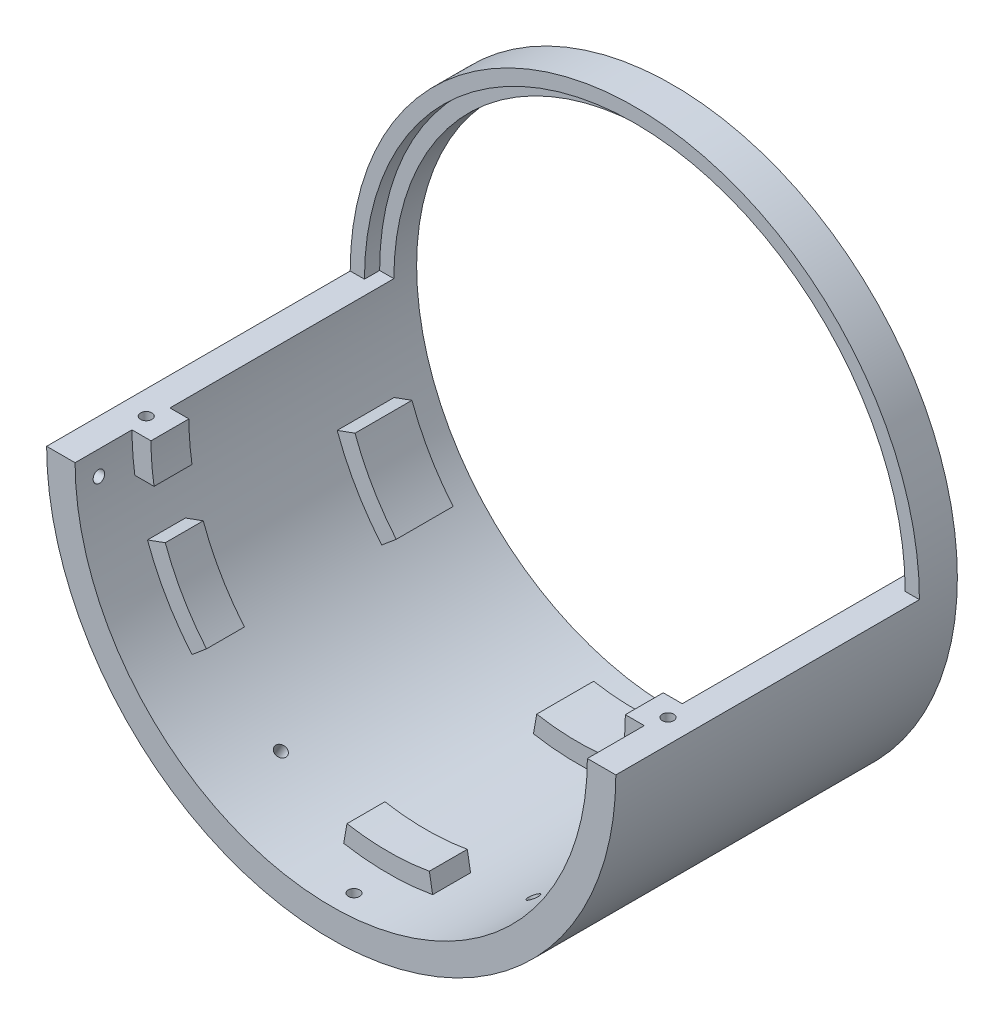
SolidWorks part; units mm, degrees
ref_plane "Front Plane" through (0, 0, 0) normal (0, 0, 1) x (1, 0, 0)
ref_plane "Top Plane" through (0, 0, 0) normal (0, 1, 0) x (1, 0, 0)
ref_plane "Right Plane" through (0, 0, 0) normal (1, 0, 0) x (0, 0, -1)
sketch "Sketch2" plane through (0, 0, 0) normal (0, 0, 1) x (1, 0, 0)
  circle A0 centre (0, 0) radius 67.5
  circle A1 centre (0, 0) radius 75
  dimension "D1" = 135
  dimension "D2" = 7.5
extrude "Boss-Extrude2" add sketch "Sketch2" along normal blind 10
sketch "Sketch3" plane through (0, 0, 10) normal (0, 0, 1) x (1, 0, 0)
  line L0 (67.5, 0) -> (75, 0)
  line L1 (-67.5, 0) -> (-75, 0)
  circle A0 centre (0, 0) radius 67.5
  circle A1 centre (0, 0) radius 75
  circle M1 centre (0, 0) radius 75
  circle M2 centre (0, 0) radius 67.5
  dimension "D1" = 135
  dimension "D2" = 7.5
extrude "Boss-Extrude3" add sketch "Sketch3" along normal blind 80 contours L1 L0 M2 M1 region at (71.25, -1.6771, 10)
sketch "Sketch5" plane through (0, 0, 10) normal (0, 0, 1) x (1, 0, 0)
  line L0 (-58.7308, -21.3763) -> (-63.4293, -23.0864)
  line L1 (-10.853, -61.5505) -> (-11.7213, -66.4745)
  line L2 (10.853, -61.5505) -> (11.7213, -66.4745)
  line L3 (-47.8778, -40.1742) -> (-51.708, -43.3882)
  line L4 (-67.5, 0) -> (-75, 0) construction
  line L5 (63.4293, -23.0864) -> (58.7308, -21.3763)
  line L6 (51.708, -43.3882) -> (47.8778, -40.1742)
  line L7 (67.5, 0) -> (75, 0) construction
  circle A0 centre (0, 0) radius 62.5
  circle A1 centre (0, 0) radius 67.5
  dimension "D1" = 125
  dimension "D2" = 5
  dimension "D3" = 20
  dimension "D4" = 4.924
  dimension "D5" = 20
  dimension "D6" = 20
  dimension "D7" = 20
  dimension "D8" = 20
extrude "Boss-Extrude4" add sketch "Sketch5" along normal blind 15 contours L0 A1 L3 A0 | L1 A1 L2 A0 | L6 A1 L5 A0 region at (-56.0339, -32.3512, 10) region at (56.0339, -32.3512, 10) region at (0, -64.7024, 10)
ref_plane "Plane1" through (0, 0, 65) normal (0, 0, 1) x (1, 0, 0)
sketch "Sketch6" plane through (0, 0, 65) normal (0, 0, 1) x (1, 0, 0)
  line L0 (-58.7308, -21.3763) -> (-63.4293, -23.0864)
  line L1 (-10.853, -61.5505) -> (-11.7213, -66.4745)
  line L2 (10.853, -61.5505) -> (11.7213, -66.4745)
  line L3 (-47.8778, -40.1742) -> (-51.708, -43.3882)
  line L5 (63.4293, -23.0864) -> (58.7308, -21.3763)
  line L6 (51.708, -43.3882) -> (47.8778, -40.1742)
  circle A0 centre (0, 0) radius 62.5
  circle A1 centre (0, 0) radius 67.5
  dimension "D1" = 125
  dimension "D2" = 5
  dimension "D3" = 20
  dimension "D4" = 4.924
  dimension "D6" = 20
  dimension "D8" = 20
extrude "Boss-Extrude5" add sketch "Sketch6" along normal blind 10 contours L0 A1 L3 A0 | L1 A1 L2 A0 | L6 A1 L5 A0 region at (-56.0339, -32.3512, 65) region at (56.0339, -32.3512, 65) region at (0, -64.7024, 65)
ref_plane "Plane2" through (67.5, 0, 0) normal (-1, 0, 0) x (0, 0, 1)
sketch "Sketch7" plane through (67.5, 0, 0) normal (-1, 0, 0) x (0, 0, 1)
  line L0 (65, 0) -> (75, 0)
  line L1 (90, 0) -> (10, 0) construction
  line L2 (65, -39.875) -> (65, 39.875) construction
  line L3 (75, 0) -> (75, -10)
  line L4 (75, -10) -> (65, -10)
  line L5 (65, -10) -> (65, 0)
  line L6 (65, -23.0864) -> (65, -43.3882) construction
  line L7 (75, -43.3882) -> (75, -23.0864) construction
  point P12 (33.0903, 2.3101)
  dimension "D2" = 10
extrude "Boss-Extrude6" add sketch "Sketch7" along normal blind 137
sketch "Sketch8" plane through (0, 0, 10) normal (0, 0, 1) x (1, 0, 0)
  line L0 (-67.5, 0) -> (67.5, 0) construction
  circle A0 centre (0, 0) radius 62.5
  dimension "D1" = 125
extrude "Cut-Extrude1" cut sketch "Sketch8" along normal blind 150
sketch "Sketch9" plane through (0, 0, 0) normal (0, 1, 0) x (1, 0, 0)
  line L0 (-75, -90) -> (-75, -10) construction
  line L1 (-41.25, -65) -> (41.25, -65) construction
  line L9 (75, -90) -> (75, -10) construction
  line L10 (62.5, -65) -> (67.5, -65) construction
  circle A0 centre (-68.75, -70) radius 1.5
  circle A2 centre (68.75, -70) radius 1.5
  dimension "D1" = 6.25
  dimension "D2" = 5
  dimension "D3" = 3
  dimension "D4" = 6.25
  dimension "D5" = 3
  dimension "D6" = 5
extrude "Cut-Extrude2" cut sketch "Sketch9" against normal blind 6.5
sketch "Sketch10" plane through (67.5, 0, 0) normal (-1, 0, 0) x (0, 0, 1)
  line L0 (90, -75) -> (90, 0) construction
  line L1 (90, 0) -> (10, 0) construction
  circle A0 centre (84, -6) radius 1.5
  dimension "D1" = 3
  dimension "D2" = 6
  dimension "D3" = 6
extrude "Cut-Extrude3" cut sketch "Sketch10" against normal blind 6.5 and the other way blind 152.5
ref_plane "Plane3" through (0, -67.5, 0) normal (0, 1, 0) x (1, 0, 0)
sketch "Sketch12" plane through (0, -67.5, 0) normal (0, 1, 0) x (1, 0, 0)
  line L0 (-67.5, -90) -> (67.5, -90) construction
  line L1 (-67.5, -90) -> (-67.5, -75) construction
  circle A0 centre (0, -84) radius 1.5
  dimension "D1" = 3
  dimension "D2" = 6
  dimension "D3" = 67.5
extrude "Cut-Extrude4" cut sketch "Sketch12" against normal blind 6.5 and the other way blind 6.5
ref_plane "Plane4" through (0, 0, 0) normal (0.866, -0.5, 0) x (0, 0, -1)
ref_plane "Plane5" through (-33.75, -58.4567, 0) normal (0.5, 0.866, 0) x (0.866, -0.5, 0)
sketch "Sketch13" plane through (-33.75, -58.4567, 0) normal (0.5, 0.866, 0) x (0.866, -0.5, 0)
  line L0 (-58.4567, -90) -> (-58.4567, -75) construction
  line L2 (-58.4567, -90) -> (67.5, -90) construction
  circle A0 centre (0.5433, -70) radius 1.5
  dimension "D1" = 3
  dimension "D2" = 59
  dimension "D3" = 20
extrude "Cut-Extrude5" cut sketch "Sketch13" against normal blind 6.5 and the other way blind 6.5
ref_plane "Plane6" through (0, 0, 0) normal (0.866, 0.5, 0) x (0, 0, -1)
ref_plane "Plane7" through (33.75, -58.4567, 0) normal (-0.5, 0.866, 0) x (0.866, 0.5, 0)
sketch "Sketch14" plane through (33.75, -58.4567, 0) normal (-0.5, 0.866, 0) x (0.866, 0.5, 0)
  line L0 (-67.5, -90) -> (58.4567, -90) construction
  line L1 (58.4567, -90) -> (58.4567, -75) construction
  circle A0 centre (-0.5433, -70) radius 1.5
  dimension "D1" = 3
  dimension "D2" = 20
  dimension "D3" = 59
extrude "Cut-Extrude6" cut sketch "Sketch14" against normal blind 6.5 and the other way blind 6.5
sketch "Sketch15" plane through (0, 0, 10) normal (0, 0, 1) x (1, 0, 0)
  line L0 (-71.25, 0) -> (-67.5, 0)
  line L1 (-67.5, 0) -> (-75, 0) construction
  line L2 (71.25, 0) -> (67.5, 0)
  circle A1 centre (0, 0) radius 71.25
  circle A2 centre (0, 0) radius 75
  arc A3 (-67.5, 0) -> (-66.7551, -10) centre (0, 0) ccw construction
  arc M1 (-67.5, 0) -> (67.5, 0) centre (0, 0) cw
  line M2 (67.5, 0) -> (75, 0)
  line M4 (-75, 0) -> (-67.5, 0)
  dimension "D1" = 150
  dimension "D2" = 3.75
extrude "Cut-Extrude7" cut sketch "Sketch15" against normal blind 4 contours A1 M2 M4 M1 region at (0, 69.6568, 10)
